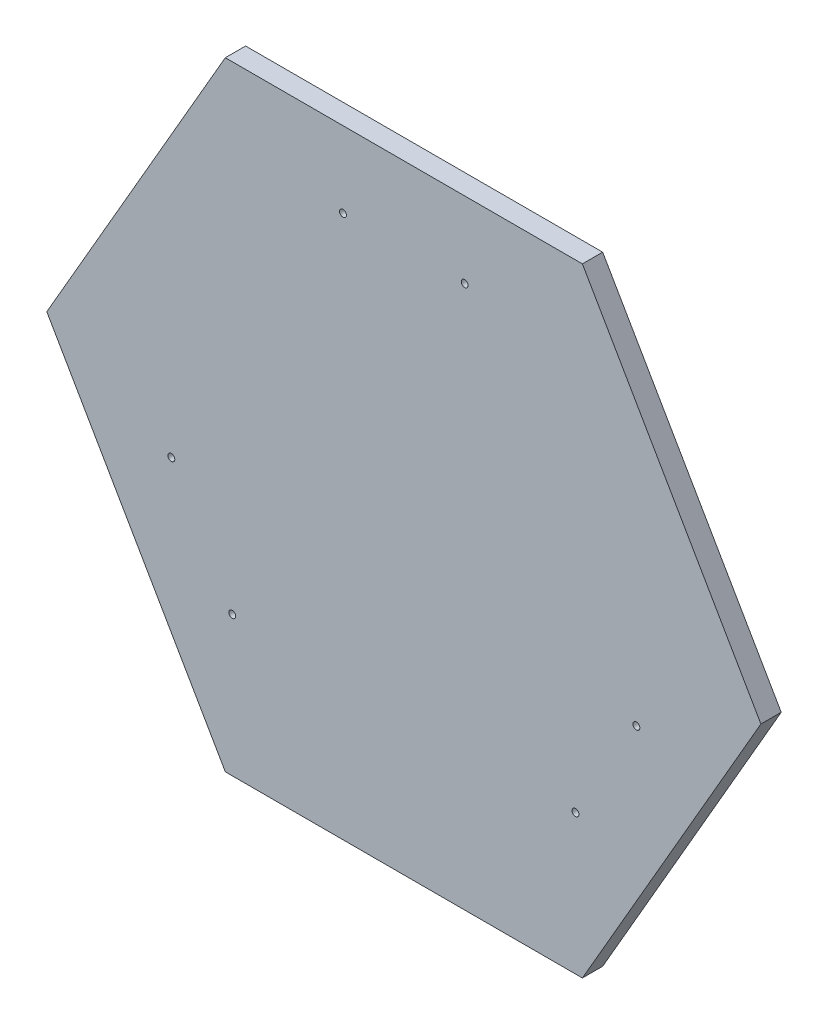
SolidWorks part; units mm, degrees
note: '?' marks a value the reader was unsure of.
material "Maple"
ref_plane "Front Plane" through (0, 0, 0) normal (0, 0, 1) x (1, 0, 0)
ref_plane "Top Plane" through (0, 0, 0) normal (0, 1, 0) x (1, 0, 0)
ref_plane "Right Plane" through (0, 0, 0) normal (1, 0, 0) x (0, 0, -1)
other "STL Graphics1"
sketch "Sketch1" plane through (0, 0, 0) normal (0, 0, 1) x (1, 0, 0)
  line L0 (0, -1000) -> (0, 49000) construction
  point P0 (30, 72)
  point P2 (30, 108)
  point P5 (-30, 72)
  point P6 (-30, 108)
  point P10 (47.3538, -61.9808)
  point P11 (78.5307, -79.9808)
  point P12 (77.3538, -10.0192)
  point P13 (108.5307, -28.0192)
  point P14 (-77.3538, -10.0192)
  point P15 (-108.5307, -28.0192)
  point P16 (-47.3538, -61.9808)
  point P17 (-78.5307, -79.9808)
  point P18 (0, 0)
  dimension "D1" = 30
  dimension "D2" = 36
  dimension "D3" = 72
  dimension "D4" = 3
sketch "Sketch2" plane through (0, 0, 0) normal (0, 0, 1) x (1, 0, 0)
  line L1 (-87.9882, 152.4) -> (-175.9764, 0)
  line L2 (-175.9764, 0) -> (-87.9882, -152.4)
  line L3 (-87.9882, -152.4) -> (87.9882, -152.4)
  line L4 (87.9882, -152.4) -> (175.9764, 0)
  line L5 (175.9764, 0) -> (87.9882, 152.4)
  line L6 (87.9882, 152.4) -> (-87.9882, 152.4)
  circle A0 centre (0, 0) radius 152.4 construction
  dimension "D1" = 304.8
extrude "Boss-Extrude1" add sketch "Sketch2" along normal mid plane 10
hole_wizard "M3 Clearance Hole1" positions "Sketch5" profile "Sketch4" hole size "M3" standard "ANSI Metric" end condition through all
sketch "Sketch5" plane through (0, 0, 5) normal (0, 0, 1) x (1, 0, 0)
  point P8 (-30, 115)
  point P11 (30, 115)
sketch "Sketch4" plane through (-30, 115, 5) normal (1, 0, 0) x (0, -1, 0)
  line L0 (0, 0) -> (0, 10)
  line L1 (0, 10) -> (1.7, 10)
  line L2 (1.7, 10) -> (1.7, 0)
  line L5 (1.7, 0) -> (0, 0)
  line L11 (0, -6.35) -> (0, 107.95) construction
  dimension "Thru Hole Dia." = 3.4
  dimension "Thru Hole Depth" = 10
ref_axis "Major-axis" through (0, 0, -20.25) along (0, 0, 1)?
pattern_circular "CirPattern1" count 3 over 360 about axis through (0, 0, 0) along (0, 0, 1) of "M3 Clearance Hole1"
